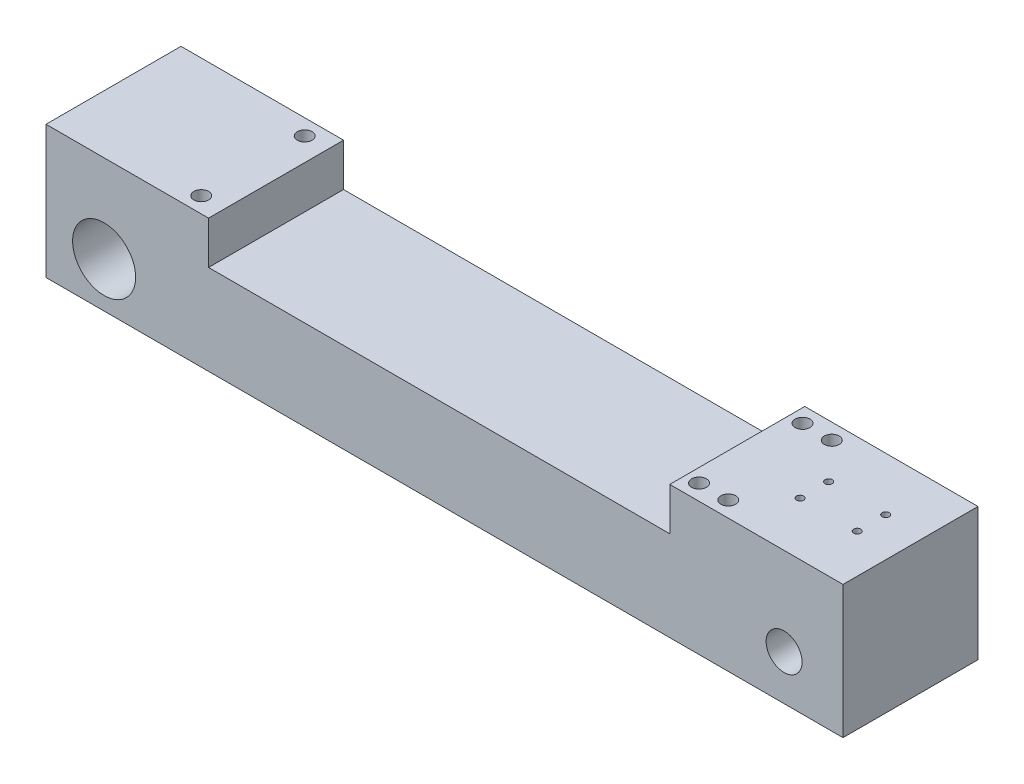
SolidWorks part; units mm, degrees
material "6061 Alloy"
ref_plane "Front Plane" through (0, 0, 0) normal (0, 0, 1) x (1, 0, 0)
ref_plane "Top Plane" through (0, 0, 0) normal (0, 1, 0) x (1, 0, 0)
ref_plane "Right Plane" through (0, 0, 0) normal (1, 0, 0) x (0, 0, -1)
sketch "Sketch1" plane through (0, 0, 0) normal (0, 0, 1) x (1, 0, 0)
  line B0 (-177.125, 0) -> (177.125, 0)
  line B1 (177.125, 0) -> (177.125, 59)
  line B2 (177.125, 59) -> (100.125, 59)
  line B3 (100.125, 59) -> (100.125, 40)
  line B4 (100.125, 40) -> (-104.875, 40)
  line B5 (-104.875, 40) -> (-104.875, 59)
  line B6 (-104.875, 59) -> (-177.125, 59)
  line B7 (-177.125, 59) -> (-177.125, 0)
  circle B8 centre (-151.3, 20) radius 14
  circle B9 centre (150.95, 20) radius 14
  arc B10 (-164.735, 9.315) -> (-164.735, 3.815) centre (-164.735, 6.565) ccw
  arc B11 (-164.735, 9.315) -> (-164.735, 3.815) centre (-164.735, 6.565) ccw
  arc B12 (-164.735, 3.815) -> (-164.735, 9.315) centre (-164.735, 6.565) ccw
  arc B13 (-164.735, 3.815) -> (-164.735, 9.315) centre (-164.735, 6.565) ccw
  arc B14 (-137.865, 3.815) -> (-137.865, 9.315) centre (-137.865, 6.565) ccw
  arc B15 (-137.865, 3.815) -> (-137.865, 9.315) centre (-137.865, 6.565) ccw
  arc B16 (-137.865, 9.315) -> (-137.865, 3.815) centre (-137.865, 6.565) ccw
  arc B17 (-137.865, 9.315) -> (-137.865, 3.815) centre (-137.865, 6.565) ccw
  arc B18 (-132.3, 17.25) -> (-132.3, 22.75) centre (-132.3, 20) ccw
  arc B19 (-132.3, 17.25) -> (-132.3, 22.75) centre (-132.3, 20) ccw
  arc B20 (-132.3, 22.75) -> (-132.3, 17.25) centre (-132.3, 20) ccw
  arc B21 (-132.3, 22.75) -> (-132.3, 17.25) centre (-132.3, 20) ccw
  arc B22 (-137.865, 30.685) -> (-137.865, 36.185) centre (-137.865, 33.435) ccw
  arc B23 (-137.865, 30.685) -> (-137.865, 36.185) centre (-137.865, 33.435) ccw
  arc B24 (-137.865, 36.185) -> (-137.865, 30.685) centre (-137.865, 33.435) ccw
  arc B25 (-137.865, 36.185) -> (-137.865, 30.685) centre (-137.865, 33.435) ccw
  arc B26 (-170.3, 17.25) -> (-170.3, 22.75) centre (-170.3, 20) ccw
  arc B27 (-170.3, 17.25) -> (-170.3, 22.75) centre (-170.3, 20) ccw
  arc B28 (-170.3, 22.75) -> (-170.3, 17.25) centre (-170.3, 20) ccw
  arc B29 (-170.3, 22.75) -> (-170.3, 17.25) centre (-170.3, 20) ccw
  arc B30 (-164.735, 30.685) -> (-164.735, 36.185) centre (-164.735, 33.435) ccw
  arc B31 (-164.735, 30.685) -> (-164.735, 36.185) centre (-164.735, 33.435) ccw
  arc B32 (-164.735, 36.185) -> (-164.735, 30.685) centre (-164.735, 33.435) ccw
  arc B33 (-164.735, 36.185) -> (-164.735, 30.685) centre (-164.735, 33.435) ccw
  arc B34 (137.515, 9.315) -> (137.515, 3.815) centre (137.515, 6.565) ccw
  arc B35 (137.515, 9.315) -> (137.515, 3.815) centre (137.515, 6.565) ccw
  arc B36 (137.515, 3.815) -> (137.515, 9.315) centre (137.515, 6.565) ccw
  arc B37 (137.515, 3.815) -> (137.515, 9.315) centre (137.515, 6.565) ccw
  arc B38 (164.385, 9.315) -> (164.385, 3.815) centre (164.385, 6.565) ccw
  arc B39 (164.385, 9.315) -> (164.385, 3.815) centre (164.385, 6.565) ccw
  arc B40 (164.385, 3.815) -> (164.385, 9.315) centre (164.385, 6.565) ccw
  arc B41 (164.385, 3.815) -> (164.385, 9.315) centre (164.385, 6.565) ccw
  arc B42 (169.95, 17.25) -> (169.95, 22.75) centre (169.95, 20) ccw
  arc B43 (169.95, 17.25) -> (169.95, 22.75) centre (169.95, 20) ccw
  arc B44 (169.95, 22.75) -> (169.95, 17.25) centre (169.95, 20) ccw
  arc B45 (169.95, 22.75) -> (169.95, 17.25) centre (169.95, 20) ccw
  arc B46 (164.385, 30.685) -> (164.385, 36.185) centre (164.385, 33.435) ccw
  arc B47 (164.385, 30.685) -> (164.385, 36.185) centre (164.385, 33.435) ccw
  arc B48 (164.385, 36.185) -> (164.385, 30.685) centre (164.385, 33.435) ccw
  arc B49 (164.385, 36.185) -> (164.385, 30.685) centre (164.385, 33.435) ccw
  arc B50 (131.95, 17.25) -> (131.95, 22.75) centre (131.95, 20) ccw
  arc B51 (131.95, 17.25) -> (131.95, 22.75) centre (131.95, 20) ccw
  arc B52 (131.95, 22.75) -> (131.95, 17.25) centre (131.95, 20) ccw
  arc B53 (131.95, 22.75) -> (131.95, 17.25) centre (131.95, 20) ccw
  arc B54 (137.515, 30.685) -> (137.515, 36.185) centre (137.515, 33.435) ccw
  arc B55 (137.515, 30.685) -> (137.515, 36.185) centre (137.515, 33.435) ccw
  arc B56 (137.515, 36.185) -> (137.515, 30.685) centre (137.515, 33.435) ccw
  arc B57 (137.515, 36.185) -> (137.515, 30.685) centre (137.515, 33.435) ccw
sketch_block_instance "Block-SecondaryBlock Sideview-1"
sketch_block "Block-SecondaryBlock Sideview"
extrude "Boss-Extrude1" add sketch "Sketch1" along normal blind 60 contours B6 B7 B0 B1 B2 B3 B4 B5 B56 B54 B52 B50 B48 B46 B44 B42 B40 B38 B36 B34 B32 B30 B28 B26 B24 B22 B20 B18 B16 B14 B12 B10 B9 B8 | B30 B32 | B26 B28 | B10 B12 | B22 B24 | B18 B20 | B14 B16 | B54 B56 | B50 B52 | B34 B36 | B38 B40 | B42 B44 | B46 B48 region at (0.6144, 25.4009, 0) region at (-164.735, 6.565, 0) region at (-137.865, 6.565, 0) region at (-132.3, 20, 0) region at (-137.865, 33.435, 0) region at (-170.3, 20, 0) region at (-164.735, 33.435, 0) region at (137.515, 6.565, 0) region at (164.385, 6.565, 0) region at (169.95, 20, 0) region at (164.385, 33.435, 0) region at (131.95, 20, 0) region at (137.515, 33.435, 0)
sketch "Sketch2" plane through (0, 59, 0) normal (0, 1, 0) x (1, 0, 0)
  line B0 (-177.125, 0) -> (177.125, 0)
  line B1 (177.125, 0) -> (177.125, -39.8)
  line B2 (177.125, -39.8) -> (-177.125, -39.8) construction
  line B3 (-177.125, -39.8) -> (-177.125, 0)
  line B4 (-177.125, -39.8) -> (-177.125, -60)
  line B5 (-177.125, -60) -> (177.125, -60)
  line B6 (177.125, -60) -> (177.125, -39.8)
  arc B7 (-118.425, -7) -> (-111.825, -7) centre (-115.125, -7) ccw
  arc B8 (-111.825, -7) -> (-118.425, -7) centre (-115.125, -7) ccw
  arc B9 (-118.425, -53) -> (-111.825, -53) centre (-115.125, -53) ccw
  arc B10 (-111.825, -53) -> (-118.425, -53) centre (-115.125, -53) ccw
  arc B11 (-132.725, -32.9) -> (-128.525, -32.9) centre (-130.625, -32.9) ccw
  arc B12 (-128.525, -32.9) -> (-132.725, -32.9) centre (-130.625, -32.9) ccw
  arc B13 (-132.725, -6.9) -> (-128.525, -6.9) centre (-130.625, -6.9) ccw
  arc B14 (-128.525, -6.9) -> (-132.725, -6.9) centre (-130.625, -6.9) ccw
  arc B15 (-173.725, -32.9) -> (-169.525, -32.9) centre (-171.625, -32.9) ccw
  arc B16 (-169.525, -32.9) -> (-173.725, -32.9) centre (-171.625, -32.9) ccw
  arc B17 (-173.725, -6.9) -> (-169.525, -6.9) centre (-171.625, -6.9) ccw
  arc B18 (-169.525, -6.9) -> (-173.725, -6.9) centre (-171.625, -6.9) ccw
  arc B19 (128.525, -6.9) -> (132.725, -6.9) centre (130.625, -6.9) ccw
  arc B20 (132.725, -6.9) -> (128.525, -6.9) centre (130.625, -6.9) ccw
  arc B21 (169.525, -6.9) -> (173.725, -6.9) centre (171.625, -6.9) ccw
  arc B22 (173.725, -6.9) -> (169.525, -6.9) centre (171.625, -6.9) ccw
  arc B23 (169.525, -32.9) -> (173.725, -32.9) centre (171.625, -32.9) ccw
  arc B24 (173.725, -32.9) -> (169.525, -32.9) centre (171.625, -32.9) ccw
  arc B25 (128.525, -32.9) -> (132.725, -32.9) centre (130.625, -32.9) ccw
  arc B26 (132.725, -32.9) -> (128.525, -32.9) centre (130.625, -32.9) ccw
  arc B27 (115.825, -53) -> (122.425, -53) centre (119.125, -53) ccw
  arc B28 (122.425, -53) -> (115.825, -53) centre (119.125, -53) ccw
  arc B29 (102.825, -53) -> (109.425, -53) centre (106.125, -53) ccw
  arc B30 (109.425, -53) -> (102.825, -53) centre (106.125, -53) ccw
  arc B31 (115.825, -7) -> (122.425, -7) centre (119.125, -7) ccw
  arc B32 (122.425, -7) -> (115.825, -7) centre (119.125, -7) ccw
  arc B33 (102.825, -7) -> (109.425, -7) centre (106.125, -7) ccw
  arc B34 (109.425, -7) -> (102.825, -7) centre (106.125, -7) ccw
sketch_block_instance "Block-SecondaryBlock Topview-1"
sketch_block "Block-SecondaryBlock Topview"
extrude "Cut-Extrude1" cut sketch "Sketch2" against normal blind 19.05 contours B7 B8 | B9 B10 | B33 B34 | B31 B32 | B29 B30 | B27 B28 region at (-115.125, 59, 7) region at (-115.125, 59, 53) region at (119.125, 59, 53) region at (106.125, 59, 53) region at (119.125, 59, 7) region at (106.125, 59, 7)
extrude "Cut-Extrude2" cut sketch "Sketch1<3>" along normal blind 19.05 contours B46 B48 | B42 B44 | B38 B40 | B54 B56 | B50 B52 | B34 B36 | B22 B24 | B18 B20 | B14 B16 | B10 B12 | B26 B28 | B30 B32 region at (-164.735, 6.565, 0) region at (-137.865, 6.565, 0) region at (-132.3, 20, 0) region at (-137.865, 33.435, 0) region at (-170.3, 20, 0) region at (-164.735, 33.435, 0) region at (137.515, 6.565, 0) region at (164.385, 6.565, 0) region at (169.95, 20, 0) region at (164.385, 33.435, 0) region at (131.95, 20, 0) region at (137.515, 33.435, 0)
sketch "Sketch1<3>" plane through (0, 0, 0) normal (0, 0, 1) x (1, 0, 0) same geometry as "Sketch1"
extrude "Cut-Extrude3" cut sketch "Sketch2<3>" along normal blind 12.7 from surface contours B23 B24 | B25 B26 | B19 B20 | B21 B22 | B11 B12 | B13 B14 | B17 B18 | B15 B16 region at (-130.625, 59, 32.9) region at (-130.625, 59, 6.9) region at (-171.625, 59, 32.9) region at (-171.625, 59, 6.9) region at (130.625, 59, 6.9) region at (171.625, 59, 6.9) region at (171.625, 59, 32.9) region at (130.625, 59, 32.9) starting at face at (0, 0, 30)
sketch "Sketch2<3>" plane through (0, 59, 0) normal (0, 1, 0) x (1, 0, 0) same geometry as "Sketch2"
sketch "Sketch3" plane through (0, 0, 0) normal (0, 0, -1) x (-1, 0, 0)
  circle A1 centre (-150.95, 20) radius 8
  circle A3 centre (-150.95, 20) radius 14
  circle A4 centre (-150.95, 20) radius 14 construction
  dimension "D2" = 16
extrude "Boss-Extrude2" add sketch "Sketch3" along normal offset from surface (28 mm away) 32 from surface up to face at (-161.985, 33.435, 0) starting at face at (164.95, 20, 60)
sketch "Sketch4" plane through (0, 59, 0) normal (0, 1, 0) x (1, 0, 0)
  line B0 (177.125, 0) -> (100.125, 0)
  line B1 (100.125, 0) -> (100.125, -60)
  line B2 (100.125, -60) -> (177.125, -60)
  line B3 (177.125, -60) -> (177.125, 0)
  line B4 (128.025, -20.5) -> (128.025, -39.5) construction
  line B5 (128.025, -20.5) -> (166.125, -20.5) construction
  line B6 (128.025, -39.5) -> (166.125, -39.5) construction
  line B7 (166.125, -20.5) -> (166.125, -39.5) construction
  circle B8 centre (134.375, -36.325) radius 1.5875
  circle B9 centre (134.375, -23.675) radius 1.5875
  circle B10 centre (159.775, -23.675) radius 1.5875
  circle B11 centre (159.775, -36.325) radius 1.5875
sketch_block_instance "Block-MotorMounting TopView 2-1"
sketch_block "Block-MotorMounting TopView 2"
extrude "Cut-Extrude4" cut sketch "Sketch4" against normal blind 6.35 contours B11 | B10 | B9 | B8 region at (134.375, 59, 36.325) region at (134.375, 59, 23.675) region at (159.775, 59, 23.675) region at (159.775, 59, 36.325)
